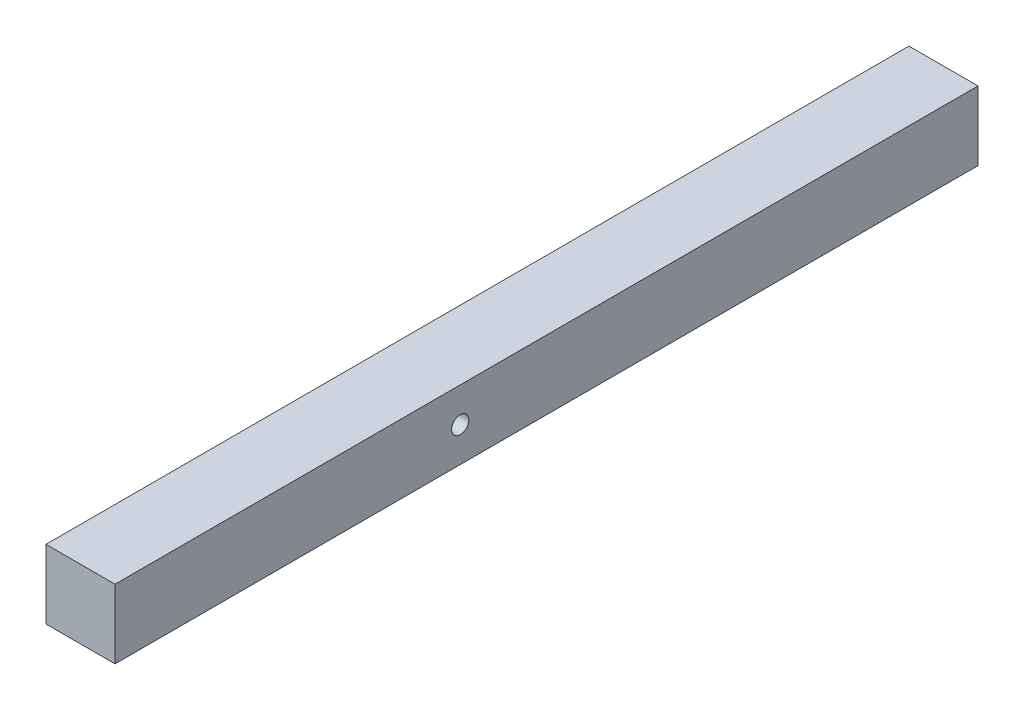
SolidWorks part; units mm, degrees
ref_plane "Front Plane" through (0, 0, 0) normal (0, 0, 1) x (1, 0, 0)
ref_plane "Top Plane" through (0, 0, 0) normal (0, 1, 0) x (1, 0, 0)
ref_plane "Right Plane" through (0, 0, 0) normal (1, 0, 0) x (0, 0, -1)
sketch "Sketch2" plane through (0, 0, 0) normal (0, 0, 1) x (1, 0, 0)
  line L1 (-50, 50) -> (50, 50)
  line L2 (-50, 50) -> (-50, -50)
  line L3 (-50, -50) -> (50, -50)
  line L4 (50, 50) -> (50, -50)
  line L5 (-50, 50) -> (50, -50) construction
  line L6 (-50, -50) -> (50, 50) construction
  point P0 (0, 0)
  dimension "D1" = 100
  dimension "D2" = 100
extrude "Boss-Extrude1" add sketch "Sketch2" against normal blind 1250
sketch "Sketch3" plane through (0, 50, 0) normal (0, 1, 0) x (1, 0, 0)
  line L0 (0, 1250) -> (0, 0) construction
  line L1 (50, 1250) -> (-50, 1250) construction
  circle A0 centre (0, 800) radius 12.5
  dimension "D1" = 25
  dimension "D2" = 450
sketch "Sketch4" plane through (50, 0, 0) normal (1, 0, 0) x (0, 0, -1)
  line L0 (0, 0) -> (1250, 0) construction
  line L1 (1250, -50) -> (1250, 50) construction
  circle A0 centre (500, 0) radius 12.5
  dimension "D1" = 25
  dimension "D2" = 500
extrude "Cut-Extrude2" cut sketch "Sketch4" against normal through all and the other way through all
